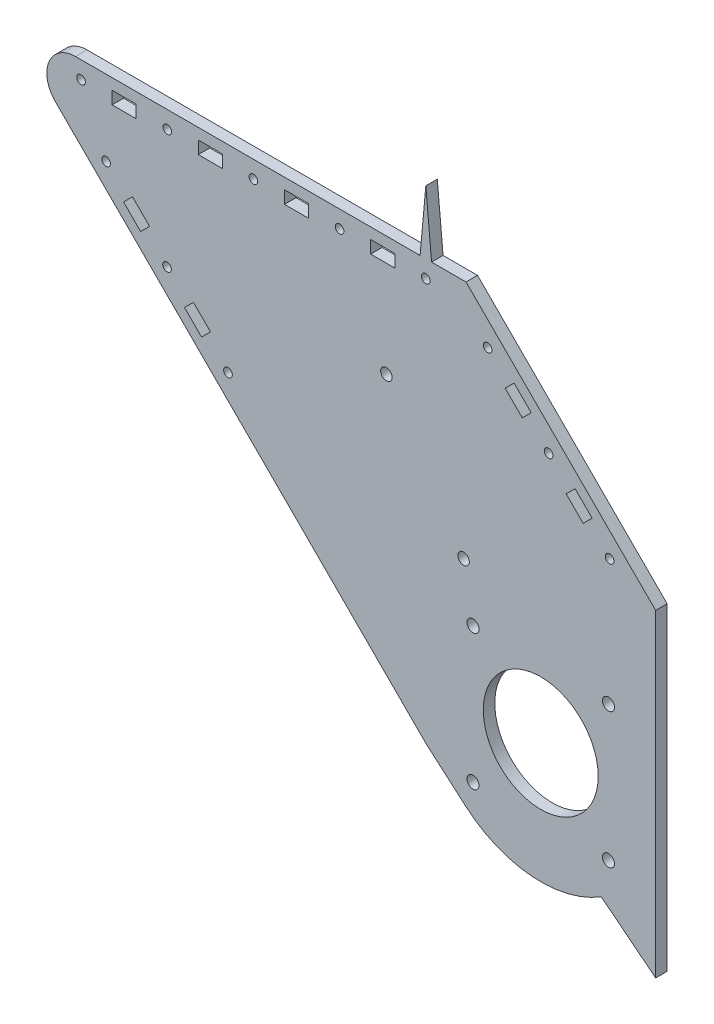
SolidWorks part; units mm, degrees
ref_plane "前视基准面" through (0, 0, 0) normal (0, 0, 1) x (1, 0, 0)
ref_plane "上视基准面" through (0, 0, 0) normal (0, 1, 0) x (1, 0, 0)
ref_plane "右视基准面" through (0, 0, 0) normal (1, 0, 0) x (0, 0, -1)
sketch "草图1" plane through (0, 0, 0) normal (0, 0, 1) x (1, 0, 0)
  line L261 (47.0274, 35.0547) -> (47.0274, 15.0547) construction
  line L315 (7.0274, -5.0025) -> (20.8108, -16.9604)
  line L316 (-52.9726, 135.0547) -> (-52.9726, 126.7057) construction
  line L332 (-112.9726, 135.0547) -> (-97.9726, 135.0547) construction
  line L334 (-42.1726, 137.2547) -> (-33.7726, 137.2547)
  line L335 (-42.1726, 137.2547) -> (-42.1726, 132.8547)
  line L336 (-42.1726, 132.8547) -> (-33.7726, 132.8547)
  line L337 (-33.7726, 137.2547) -> (-33.7726, 132.8547)
  line L338 (-42.1726, 137.2547) -> (-33.7726, 132.8547) construction
  line L339 (-42.1726, 132.8547) -> (-33.7726, 137.2547) construction
  line L389 (-114.8877, 141.0547) -> (21.0274, 141.0547)
  line L390 (-22.9726, 135.0547) -> (-22.9726, 144.5851) construction
  line L395 (-37.9726, 135.0547) -> (-7.9726, 135.0547) construction
  line L418 (87.0274, 75.0547) -> (21.0274, 141.0547)
  line L419 (-3.7726, 132.8547) -> (-12.1726, 137.2547) construction
  line L420 (-3.7726, 137.2547) -> (-12.1726, 132.8547) construction
  line L421 (7.0274, 135.0547) -> (-7.9726, 135.0547) construction
  line L422 (-12.1726, 137.2547) -> (-12.1726, 132.8547)
  line L423 (-3.7726, 132.8547) -> (-12.1726, 132.8547)
  line L424 (-3.7726, 137.2547) -> (-3.7726, 132.8547)
  line L443 (-3.7726, 137.2547) -> (-12.1726, 137.2547)
  line L444 (-102.1726, 137.2547) -> (-93.7726, 132.8547) construction
  line L445 (-102.1726, 132.8547) -> (-93.7726, 137.2547) construction
  line L446 (7.0274, -5.0025) -> (-139.0298, 141.0547) construction
  line L447 (-67.9726, 135.0547) -> (-97.9726, 135.0547) construction
  line L448 (47.0274, 15.0547) -> (7.0431, -54.2363) construction
  line L449 (-63.7726, 132.8547) -> (-72.1726, 137.2547) construction
  line L483 (-63.7726, 137.2547) -> (-72.1726, 132.8547) construction
  line L515 (47.0274, 35.0547) -> (47.0274, 135.0547) construction
  line L516 (47.0274, 135.0547) -> (-52.9726, 135.0547) construction
  line L517 (-102.1726, 137.2547) -> (-93.7726, 137.2547)
  line L518 (-102.1726, 137.2547) -> (-102.1726, 132.8547)
  line L519 (-102.1726, 132.8547) -> (-93.7726, 132.8547)
  line L520 (-93.7726, 137.2547) -> (-93.7726, 132.8547)
  line L521 (-72.1726, 137.2547) -> (-72.1726, 132.8547)
  line L522 (-63.7726, 132.8547) -> (-72.1726, 132.8547)
  line L523 (-63.7726, 137.2547) -> (-63.7726, 132.8547)
  line L524 (-63.7726, 137.2547) -> (-72.1726, 137.2547)
  line L525 (7.0274, -5.0025) -> (-7.4159, -49.5482) construction
  line L551 (7.0274, -5.0025) -> (87.0274, -5.0025) construction
  line L552 (7.0274, -5.0025) -> (7.0274, 75.0547) construction
  line L553 (7.0274, 75.0547) -> (87.0274, 75.0547) construction
  line L554 (87.0274, -5.0025) -> (87.0274, 75.0547)
  line L555 (87.0274, -5.0025) -> (17.0006, -65.7205) construction
  line L556 (21.4033, 132.1936) -> (81.3921, 72.2048) construction
  line L557 (54.0274, 108.0547) -> (35.0674, 89.0947) construction
  line L558 (43.7037, 113.0045) -> (34.6527, 115.8329) construction
  line L559 (55.8659, 94.6197) -> (61.8056, 88.68)
  line L576 (55.8659, 94.6197) -> (58.9772, 97.731)
  line L577 (58.9772, 97.731) -> (64.9169, 91.7913)
  line L578 (61.8056, 88.68) -> (64.9169, 91.7913)
  line L579 (55.8659, 94.6197) -> (64.9169, 91.7913) construction
  line L580 (58.9772, 97.731) -> (61.8056, 88.68) construction
  line L581 (40.5924, 109.8932) -> (37.764, 118.9442) construction
  line L582 (34.6527, 115.8329) -> (37.764, 118.9442)
  line L583 (43.7037, 113.0045) -> (37.764, 118.9442)
  line L584 (40.5924, 109.8932) -> (43.7037, 113.0045)
  line L585 (40.5924, 109.8932) -> (34.6527, 115.8329)
  line L586 (60.3914, 93.2055) -> (58.8358, 91.6499) construction
  line L587 (39.1782, 114.4187) -> (37.6226, 112.8631) construction
  line L594 (73.2276, -16.9678) -> (87.0274, -5.0025)
  line L599 (-90.2039, 92.2289) -> (-121.9587, 123.9837)
  line L600 (-73.8521, 87.4736) -> (-76.9634, 84.3624)
  line L605 (-25.9726, 27.9975) -> (-21.7299, 32.2402) construction
  line L607 (-83.0445, 93.5547) -> (-87.2872, 89.3121) construction
  line L608 (-90.2039, 92.2289) -> (7.0274, -5.0025)
  line L621 (-83.0445, 93.5547) -> (-61.8313, 72.3415) construction
  line L622 (-73.8521, 87.4736) -> (-67.9124, 81.5339)
  line L623 (47.0274, 15.0547) -> (89.2922, -52.8694) construction
  line L624 (89.2922, -52.8694) -> (7.0274, -54.2273) construction
  line L625 (-76.9634, 84.3624) -> (-71.0237, 78.4227)
  line L630 (-67.9124, 81.5339) -> (-71.0237, 78.4227)
  line L631 (-73.8521, 87.4736) -> (-71.0237, 78.4227) construction
  line L632 (-82.9726, 135.0547) -> (-82.9726, 64.2144) construction
  line L633 (-76.9634, 84.3624) -> (-67.9124, 81.5339) construction
  line L634 (-89.1256, 102.7471) -> (-92.2369, 99.6359)
  line L635 (-92.2369, 99.6359) -> (-98.1766, 105.5756)
  line L636 (-95.0653, 108.6868) -> (-98.1766, 105.5756)
  line L637 (-89.1256, 102.7471) -> (-95.0653, 108.6868)
  line L638 (-22.9726, 135.0547) -> (-22.9726, 124.9547) construction
  line L639 (-22.9726, 124.9547) -> (47.0274, 15.0547) construction
  circle A39 centre (-52.9726, 135.0547) radius 1.5
  circle A42 centre (47.0274, 15.0547) radius 20
  circle A49 centre (-22.9726, 135.0547) radius 1.5
  circle A69 centre (7.0274, 135.0547) radius 1.5
  circle A92 centre (-112.9726, 135.0547) radius 1.5
  circle A93 centre (-82.9726, 135.0547) radius 1.5
  circle A94 centre (7.0431, -54.2363) radius 5.2 construction
  circle A96 centre (7.0431, -54.2363) radius 15.2 construction
  circle A98 centre (49.7848, 103.8121) radius 1.5
  circle A99 centre (70.998, 82.5989) radius 1.5
  circle A100 centre (28.5716, 125.0253) radius 1.5
  circle A107 centre (70.5974, 38.6247) radius 2.1
  circle A108 centre (70.5974, -8.5153) radius 2.1
  circle A109 centre (23.4574, -8.5153) radius 2.1
  circle A110 centre (23.4574, 38.6247) radius 2.1
  arc A111 (73.2276, -16.9678) -> (20.8108, -16.9604) centre (47.0235, 13.2537) cw
  arc A115 (-114.8877, 141.0547) -> (-121.9587, 123.9837) centre (-114.8877, 131.0547) ccw
  circle A116 centre (-83.0445, 93.5547) radius 1.5
  circle A117 centre (-61.8313, 72.3415) radius 1.5
  circle A118 centre (-104.2577, 114.7679) radius 1.5
  circle A121 centre (20.1663, 57.2267) radius 2
  circle A122 centre (-6.6949, 99.3988) radius 2
  point P5 (210.9534, 218.4629)
  point P6 (288.6284, 218.4629)
  point P54 (-105.4726, 135.0547)
  point P60 (60.3914, 93.2055)
  point P88 (-72.4379, 82.9481)
  point P115 (47.016, -39.6951)
  dimension "D1" = 40
  dimension "D3" = 40
  dimension "D5" = 23.57
  dimension "D4" = 4.2
  dimension "D6" = 23.57
  dimension "D2" = 40
  dimension "D7" = 6
  dimension "D12" = 3
  dimension "D19" = 10.4
  dimension "D20" = 10
  dimension "D22" = 3
  dimension "D8" = 30
  dimension "D28" = 40
  dimension "D26" = 10
  dimension "D17" = 10.1
  dimension "D29" = 50
  dimension "D30" = 50
  dimension "D9" = 15
  dimension "D10" = 15
  dimension "D11" = 8.4
  dimension "D13" = 4.4
  dimension "D14" = 6
  dimension "D15" = 45
  dimension "D16" = 41.5
  dimension "D18" = 80
  dimension "D21" = 6
  dimension "D23" = 15
  dimension "D24" = 8.4
  dimension "D25" = 4.4
  dimension "D27" = 4
extrude "凸台-拉伸1" add sketch "草图1" along normal blind 4
sketch "草图2" plane through (0, 0, 4) normal (0, 0, 1) x (1, 0, 0)
  line L0 (87.0274, -5.0025) -> (87.0274, -35.7541)
  line L1 (87.0274, -35.7541) -> (68.0896, -20.7495)
  line L2 (68.0896, -20.7495) -> (87.0274, -5.0025)
  arc A0 (20.8108, -16.9604) -> (73.2276, -16.9678) centre (47.0235, 13.2537) ccw construction
extrude "凸台-拉伸2" add sketch "草图2" against normal blind 4
sketch "草图3" plane through (0, 0, 4) normal (0, 0, 1) x (1, 0, 0)
  line L6 (21.0274, 141.0547) -> (-114.8877, 141.0547) construction
  line L10 (7.0274, 135.0547) -> (7.0274, 141.0547) construction
  line L11 (7.0274, 141.0547) -> (7.0274, 163.0547) construction
  line L12 (7.0274, 141.0547) -> (5.0274, 141.0547)
  line L13 (5.0274, 141.0547) -> (7.0274, 163.0547)
  line L14 (7.0274, 141.0547) -> (9.0274, 141.0547)
  line L15 (9.0274, 141.0547) -> (7.0274, 163.0547)
extrude "凸台-拉伸4" add sketch "草图3" against normal blind 4
